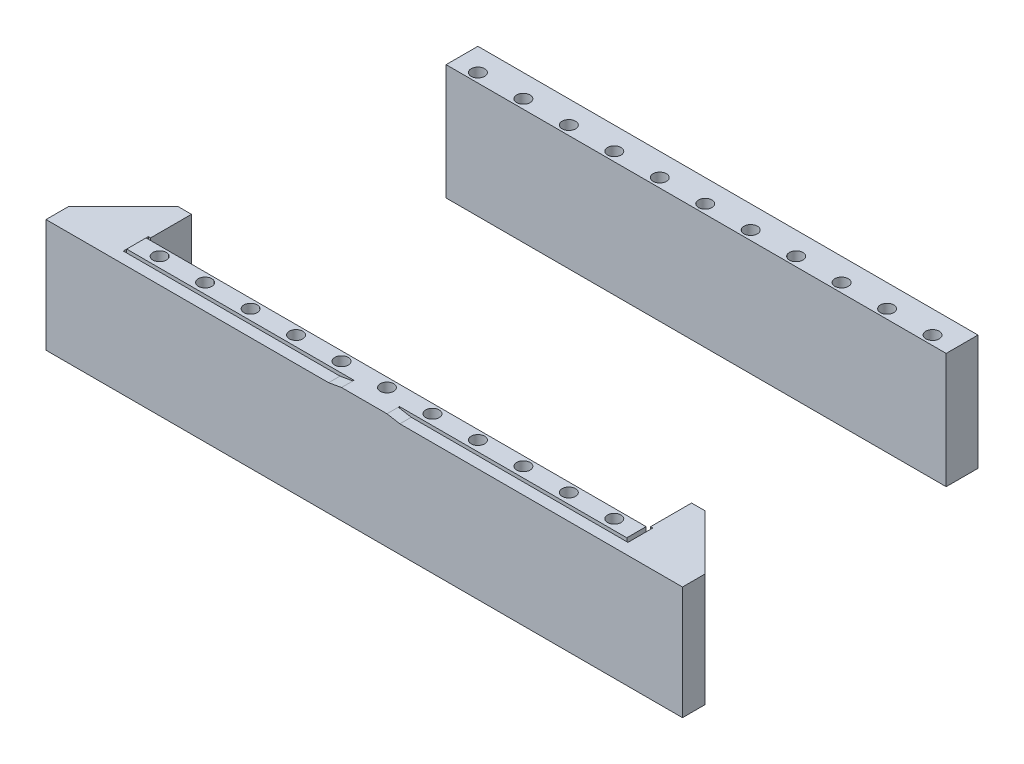
SolidWorks part; units mm, degrees
ref_plane "Front Plane" through (0, 0, 0) normal (0, 0, 1) x (1, 0, 0)
ref_plane "Top Plane" through (0, 0, 0) normal (0, 1, 0) x (1, 0, 0)
ref_plane "Right Plane" through (0, 0, 0) normal (1, 0, 0) x (0, 0, -1)
sketch "Sketch1" plane through (0, 0, 0) normal (0, 1, 0) x (1, 0, 0)
  line L1 (-55, 40) -> (55, 40)
  line L2 (-55, 40) -> (-55, -40)
  line L3 (-55, -40) -> (55, -40)
  line L4 (55, 40) -> (55, -40)
  line L5 (-55, 40) -> (55, -40) construction
  line L6 (-55, -40) -> (55, 40) construction
  point P0 (0, 0)
  dimension "D1" = 80
  dimension "D2" = 110
extrude "Boss-Extrude1" add sketch "Sketch1" along normal blind 25.4
sketch "Sketch2" plane through (55, 0, 0) normal (1, 0, 0) x (0, 0, -1)
  line L0 (-40, 25.4) -> (40, 25.4) construction
  line L1 (-33, 1.4) -> (33, 1.4)
  line L2 (-33, 1.4) -> (-33, 25.4)
  line L3 (-33, 25.4) -> (33, 25.4)
  line L4 (33, 1.4) -> (33, 25.4)
  line L5 (-33, 1.4) -> (33, 25.4) construction
  line L6 (-33, 25.4) -> (33, 1.4) construction
  point P0 (0, 13.4)
  dimension "D1" = 66
  dimension "D2" = 24
extrude "Cut-Extrude1" cut sketch "Sketch2" against normal through all
sketch "Sketch3" plane through (0, 0, 0) normal (0, -1, 0) x (1, 0, 0)
  circle A0 centre (0, 35) radius 1.475
  circle A1 centre (0, -35) radius 1.475
  dimension "D1" = 2.95
  dimension "D2" = 35
  dimension "D3" = 35
extrude "Cut-Extrude2" cut sketch "Sketch3" against normal through all
pattern_linear "LPattern1" count 6 spacing 10 along (1, 0, 0) count 6 spacing 10 along (-1, 0, 0) of "Cut-Extrude2"
sketch "Sketch4" plane through (0, 0, 0) normal (0, 1, 0) x (1, 0, 0)
  line L0 (-55, -33) -> (55, -33) construction
  line L1 (55, -40) -> (58, -40)
  line L2 (55, -40) -> (55, -37.5)
  line L3 (55, -37.5) -> (55.5, -37.5)
  line L4 (58, -40) -> (58, -37.5)
  line L6 (58, -37.5) -> (58, -23)
  line L7 (58, -23) -> (55.5, -23)
  line L8 (55.5, -37.5) -> (55.5, -23)
  line L9 (55, -40) -> (55, -33) construction
  dimension "D1" = 2.5
  dimension "D2" = 10
  dimension "D3" = 2.5
  dimension "D4" = 0.5
extrude "Boss-Extrude2" add sketch "Sketch4" along normal offset from surface (24.9 mm away) 0.5 up to face at (-50, 25.4, 33.525)
sketch "Sketch11" plane through (0, 1.4, 0) normal (0, 1, 0) x (1, 0, 0)
  line L0 (-55, 33) -> (55, 33) construction
  line L1 (55, -33) -> (45, -33)
  line L2 (55, -33) -> (55, 33)
  line L3 (55, 33) -> (45, 33)
  line L4 (45, -33) -> (45, 33)
  dimension "D1" = 10
extrude "Cut-Extrude7" cut sketch "Sketch11" against normal through all
sketch "Sketch12" plane through (0, 0, 0) normal (0, 1, 0) x (1, 0, 0)
  line L0 (55, -40) -> (55, -33) construction
  line L1 (55.5, -23) -> (55, -23)
  line L2 (55.5, -23) -> (55.5, -32)
  line L3 (55.5, -32) -> (55, -32)
  line L4 (55, -23) -> (55, -32)
  line L5 (-55, -33) -> (55, -33) construction
  dimension "D1" = 1
extrude "Boss-Extrude5" add sketch "Sketch12" along normal up to surface (24.9 mm away) up to face at (56.1667, 24.9, 33.5)
sketch "Sketch5" plane through (0, 25.4, 0) normal (0, 1, 0) x (1, 0, 0)
  line L1 (55, -37.5) -> (5, -37.5)
  line L2 (55, -37.5) -> (55, -37.25)
  line L3 (55, -37.25) -> (5, -37.25)
  line L4 (5, -37.5) -> (5, -37.25)
  dimension "D1" = 0.25
  dimension "D2" = 5
extrude "Cut-Extrude3" cut sketch "Sketch5" against normal through all
sketch "Sketch6" plane through (0, 25.4, 0) normal (0, 1, 0) x (1, 0, 0)
  line L1 (55, -40) -> (5, -40)
  line L2 (55, -40) -> (55, -37.5)
  line L3 (55, -37.5) -> (5, -37.5)
  line L4 (5, -40) -> (5, -37.5)
extrude "Cut-Extrude4" cut sketch "Sketch6" against normal up to surface (0.5 mm away) up to face at (55.875, 24.9, 33.125)
sketch "Sketch7" plane through (0, 0, 0) normal (0, 1, 0) x (1, 0, 0)
  line L0 (55, -37.25) -> (55, -33) construction
  line L1 (58, -40) -> (70, -40)
  line L2 (58, -40) -> (58, -35)
  line L3 (58, -35) -> (70, -35)
  line L4 (70, -40) -> (70, -35)
  line L6 (-55, -33) -> (55, -33) construction
  dimension "D1" = 2
  dimension "D2" = 15
extrude "Boss-Extrude3" add sketch "Sketch7" along normal up to surface (24.9 mm away) up to face at (43.375, 24.9, 33.125)
sketch "Sketch8" plane through (0, 0, 0) normal (0, 1, 0) x (1, 0, 0)
  line L0 (58, -23) -> (70, -35)
  line L1 (70, -35) -> (58, -35)
  line L2 (58, -35) -> (58, -23)
extrude "Boss-Extrude4" add sketch "Sketch8" along normal up to surface (24.9 mm away) up to face at (48.7, 24.9, 33.5)
chamfer "Chamfer1" distance 0.5 angle 80 1 edges at (5, 24.9, 38.75) first distance on face at (5, 16.7667, 38.25)
sketch "Sketch9" plane through (0, 25.4, 0) normal (0, 1, 0) x (1, 0, 0)
  line L0 (-55, -40) -> (5, -40) construction
  line L1 (-55, 40) -> (0, 40)
  line L2 (-55, 40) -> (-55, -40)
  line L3 (-55, -40) -> (0, -40)
  line L4 (0, 40) -> (0, -40)
extrude "Cut-Extrude5" cut sketch "Sketch9" against normal through all
mirror "Mirror1" about plane through (0, 0, -40) normal (1, 0, 0) of bodies 110
sketch "Sketch10" plane through (0, 1.4, 0) normal (0, 1, 0) x (1, 0, 0)
  line L4 (45, 33) -> (-45, 33)
  line L5 (-45, 33) -> (-45, -33)
  line L6 (-45, -33) -> (45, -33)
  line L7 (-45, 33) -> (-45, -33)
  line L8 (45, 33) -> (-45, 33)
  line L10 (-45, -33) -> (45, -33)
  line L12 (45, -33) -> (45, 33)
  line L13 (45, -33) -> (45, 33)
  dimension "D1" = 0
extrude "Cut-Extrude6" cut sketch "Sketch10" against normal through all
move or copy body "Body-Move/Copy1" [suppressed] bodies to move or copy 114 115 placed by mates yes parameters "D1"=0, "D2"=0, "D3"=0
move or copy body "Body-Move/Copy2" [suppressed] bodies to move or copy 119 placed by mates yes parameters "D1"=0, "D2"=0, "D3"=0
other "Distance1" [suppressed] parameters "D1"=2
equation "\"D3@Sketch3\"=\"D2@Sketch3\""
